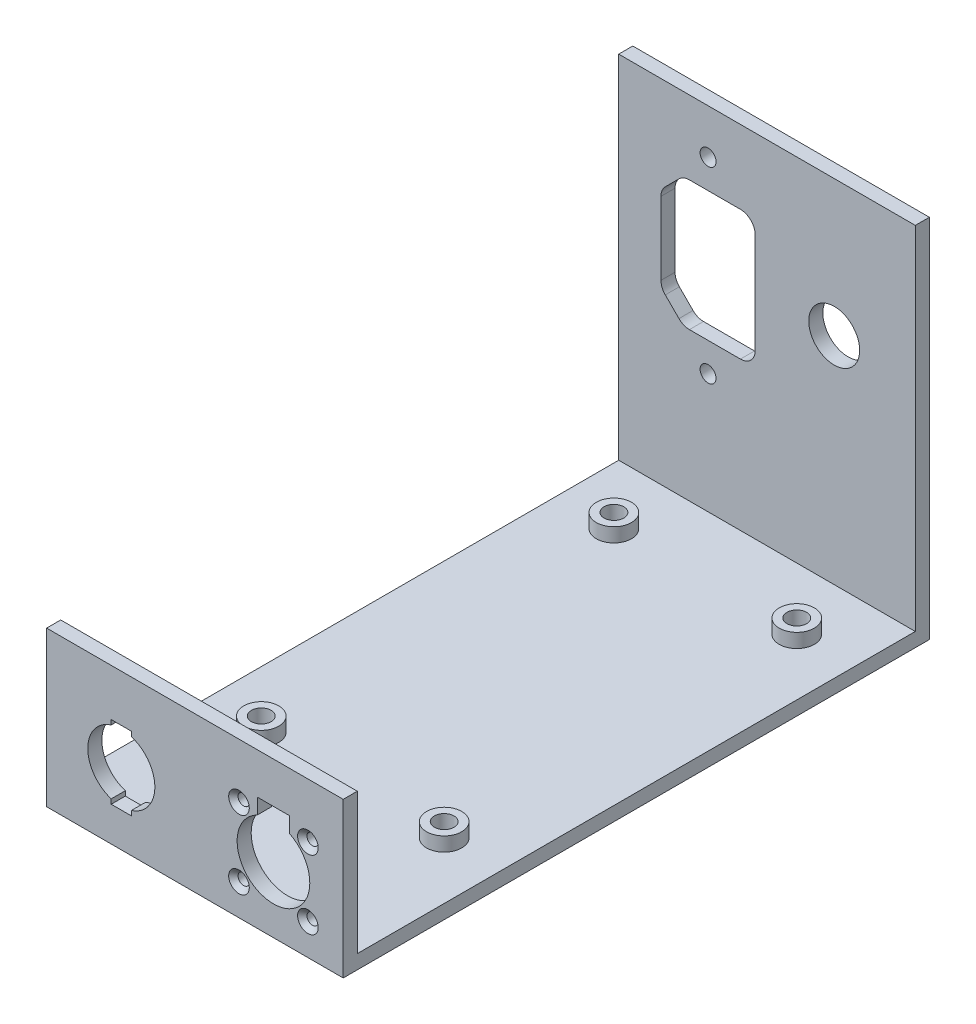
SolidWorks part; units mm, degrees
ref_plane "Спереди" through (0, 0, 0) normal (0, 0, 1) x (1, 0, 0)
ref_plane "Сверху" through (0, 0, 0) normal (0, 1, 0) x (1, 0, 0)
ref_plane "Справа" through (0, 0, 0) normal (1, 0, 0) x (0, 0, -1)
sketch "Эскиз2" plane through (0, 0, 0) normal (0, -1, 0) x (1, 0, 0)
  circle A0 centre (19.5, 37.6) radius 3.75
  circle A1 centre (19.5, -37.6) radius 3.75
  circle A2 centre (-19.5, -37.6) radius 3.75
  circle A3 centre (-19.5, 37.6) radius 3.75
  dimension "D1" = 7.5
extrude "Бобышка-Вытянуть1" add sketch "Эскиз2" along normal blind 3
sketch "Эскиз3" plane through (0, -3, 0) normal (0, -1, 0) x (1, 0, 0)
  line L0 (26.625, 41.25) -> (26.625, -41.25) construction
  line L1 (-31.625, 71.25) -> (31.625, 71.25)
  line L2 (-31.625, 71.25) -> (-31.625, -53.75)
  line L3 (-31.625, -53.75) -> (31.625, -53.75)
  line L4 (31.625, 71.25) -> (31.625, -53.75)
  line L5 (-31.625, 71.25) -> (31.625, -53.75) construction
  line L6 (-31.625, -53.75) -> (31.625, 71.25) construction
  line L8 (-23.625, 41.25) -> (23.625, 41.25) construction
  line L9 (-26.625, 41.25) -> (-26.625, -41.25) construction
  point P0 (0, 8.75)
  dimension "D1" = 5
  dimension "D2" = 125
  dimension "D3" = 30
  dimension "D4" = 5
extrude "Бобышка-Вытянуть2" add sketch "Эскиз3" along normal blind 3
sketch "Эскиз4" plane through (0, 0, 0) normal (0, 1, 0) x (1, 0, 0)
  circle A0 centre (19.5, 37.6) radius 2.1
  circle A1 centre (19.5, -37.6) radius 2.1
  circle A2 centre (-19.5, -37.6) radius 2.1
  circle A3 centre (-19.5, 37.6) radius 2.1
  dimension "D1" = 4.2
extrude "Вырез-Вытянуть1" cut sketch "Эскиз4" against normal blind 4
sketch "Эскиз5" plane through (0, -3, 0) normal (0, 1, 0) x (1, 0, 0)
  line L0 (31.625, 53.75) -> (31.625, -71.25) construction
  line L1 (-31.625, -71.25) -> (31.625, -71.25)
  line L2 (-31.625, -71.25) -> (-31.625, -68.25)
  line L3 (-31.625, -68.25) -> (31.625, -68.25)
  line L4 (31.625, -71.25) -> (31.625, -68.25)
  dimension "D1" = 3
extrude "Бобышка-Вытянуть3" add sketch "Эскиз5" along normal blind 30
sketch "Эскиз8" plane through (0, 0, 71.25) normal (0, 0, 1) x (1, 0, 0)
  line L6 (20.1954, 14.9397) -> (20.1954, 18.25)
  line L7 (20.1954, 18.25) -> (13.2954, 18.25)
  line L8 (13.2954, 18.25) -> (13.2954, 14.9397)
  line L9 (20.1954, 14.9397) -> (20.1954, 18.25)
  line L10 (20.1954, 18.25) -> (13.2954, 18.25)
  line L11 (13.2954, 18.25) -> (13.2954, 14.9397)
  arc A2 (13.2954, 14.9397) -> (20.1954, 14.9397) centre (16.7454, 8) ccw
  arc A3 (13.2954, 14.9397) -> (20.1954, 14.9397) centre (16.7454, 8) ccw
  dimension "D1" = 0.15
extrude "Вырез-Вытянуть2" cut sketch "Эскиз8" against normal blind 10
hole_wizard "Зенковка для винта с полупотайной головкой M21" positions "Эскиз9" profile "Эскиз11" countersink size "M2" standard "DIN"
sketch "Эскиз9" plane through (0, 0, 71.25) normal (0, 0, 1) x (1, 0, 0)
  circle A0 centre (9.3954, 0.65) radius 1.2 construction
  circle A1 centre (24.0954, 0.65) radius 1.2 construction
  circle A2 centre (9.3954, 15.35) radius 1.2 construction
  circle A3 centre (24.0954, 15.35) radius 1.2 construction
  circle A4 centre (9.3954, 0.65) radius 1.2 construction
  circle A5 centre (24.0954, 0.65) radius 1.2 construction
  circle A6 centre (9.3954, 15.35) radius 1.2 construction
  circle A7 centre (24.0954, 15.35) radius 1.2 construction
  point P1 (9.3954, 0.65)
  point P3 (24.0954, 0.65)
  point P5 (9.3954, 15.35)
  point P7 (24.0954, 15.35)
sketch "Эскиз11" plane through (9.3954, 0.65, 71.25) normal (1, 0, 0) x (0, -1, 0)
  line L0 (0, 0) -> (0, 5.721)
  line L1 (0, 5.721) -> (1.2, 5)
  line L2 (1.2, 5) -> (1.2, 1)
  line L3 (1.2, 1) -> (2.2, 0)
  line L5 (2.2, 0) -> (0, 0)
  line L6 (-1.2, 1) -> (-2.2, 0) construction
  line L10 (0, 5.721) -> (-1.2, 5) construction
  line L11 (0, -6.35) -> (0, 107.95) construction
  dimension "Диаметр отверстия" = 2.4
  dimension "Глубина отверстия" = 5
  dimension "Диаметр передней зенковки" = 4.4
  dimension "Угол передней зенковки" = 90
  dimension "Угол заточки сверла" = 118
sketch "Эскиз12" plane through (0, -3, 0) normal (0, 1, 0) x (1, 0, 0)
  line L0 (-31.625, -68.25) -> (-31.625, 53.75) construction
  line L1 (31.625, 53.75) -> (-31.625, 53.75)
  line L2 (31.625, 53.75) -> (31.625, 50.75)
  line L3 (31.625, 50.75) -> (-31.625, 50.75)
  line L4 (-31.625, 53.75) -> (-31.625, 50.75)
  dimension "D1" = 3
extrude "Бобышка-Вытянуть4" add sketch "Эскиз12" along normal blind 75
sketch "Эскиз13" plane through (0, 0, -50.75) normal (0, 0, 1) x (1, 0, 0)
  line L12 (-16.5476, 28.6612) -> (-5.6652, 28.6612)
  line L13 (-2.5152, 31.8112) -> (-2.5152, 53.1612)
  line L14 (-5.6652, 56.3112) -> (-16.5476, 56.3112)
  line L15 (-18.775, 55.3886) -> (-21.6926, 52.471)
  line L16 (-22.6152, 50.2436) -> (-22.6152, 34.7289)
  line L17 (-21.6926, 32.5015) -> (-18.775, 29.5839)
  line L18 (-16.5476, 28.6612) -> (-5.6652, 28.6612)
  line L19 (-2.5152, 31.8112) -> (-2.5152, 53.1612)
  line L20 (-5.6652, 56.3112) -> (-16.5476, 56.3112)
  line L21 (-18.775, 55.3886) -> (-21.6926, 52.471)
  line L22 (-22.6152, 50.2436) -> (-22.6152, 34.7289)
  line L23 (-21.6926, 32.5015) -> (-18.775, 29.5839)
  arc A12 (-18.775, 29.5839) -> (-16.5476, 28.6612) centre (-16.5476, 31.8112) ccw
  arc A13 (-5.6652, 28.6612) -> (-2.5152, 31.8112) centre (-5.6652, 31.8112) ccw
  arc A14 (-2.5152, 53.1612) -> (-5.6652, 56.3112) centre (-5.6652, 53.1612) ccw
  arc A15 (-16.5476, 56.3112) -> (-18.775, 55.3886) centre (-16.5476, 53.1612) ccw
  arc A16 (-21.6926, 52.471) -> (-22.6152, 50.2436) centre (-19.4652, 50.2436) ccw
  arc A17 (-22.6152, 34.7289) -> (-21.6926, 32.5015) centre (-19.4652, 34.7289) ccw
  arc A18 (-18.775, 29.5839) -> (-16.5476, 28.6612) centre (-16.5476, 31.8112) ccw
  arc A19 (-5.6652, 28.6612) -> (-2.5152, 31.8112) centre (-5.6652, 31.8112) ccw
  arc A20 (-2.5152, 53.1612) -> (-5.6652, 56.3112) centre (-5.6652, 53.1612) ccw
  arc A21 (-16.5476, 56.3112) -> (-18.775, 55.3886) centre (-16.5476, 53.1612) ccw
  arc A22 (-21.6926, 52.471) -> (-22.6152, 50.2436) centre (-19.4652, 50.2436) ccw
  arc A23 (-22.6152, 34.7289) -> (-21.6926, 32.5015) centre (-19.4652, 34.7289) ccw
  dimension "D1" = 0.15
extrude "Вырез-Вытянуть3" cut sketch "Эскиз13" against normal through all
hole_wizard "Отверстие с зазором M31" positions "Эскиз14" profile "Эскиз15" hole size "M3" standard "DIN"
sketch "Эскиз14" plane through (0, 0, -53.75) normal (0, 0, -1) x (-1, 0, 0)
  point P0 (12.5652, 22.4862)
  point P3 (12.5652, 62.4862)
sketch "Эскиз15" plane through (-12.5652, 22.4862, -53.75) normal (1, 0, 0) x (0, 1, 0)
  line L0 (0, 0) -> (0, 11.0215)
  line L1 (0, 11.0215) -> (1.7, 10)
  line L2 (1.7, 10) -> (1.7, 0)
  line L5 (1.7, 0) -> (0, 0)
  line L10 (0, 11.0215) -> (-1.7, 10) construction
  line L11 (0, -6.35) -> (0, 107.95) construction
  dimension "Диаметр отверстия" = 3.4
  dimension "Глубина отверстия" = 10
  dimension "Угол заточки сверла" = 118
sketch "Эскиз16" plane through (0, 0, -50.75) normal (0, 0, 1) x (1, 0, 0)
  circle A2 centre (14.3322, 42.9731) radius 5.425
  circle A3 centre (14.3322, 42.9731) radius 5.425
  dimension "D1" = 0.15
extrude "Вырез-Вытянуть4" cut sketch "Эскиз16" against normal through all
sketch "Эскиз17" plane through (0, 0, 68.25) normal (0, 0, -1) x (-1, 0, 0)
  line L2 (17.6969, 0.8798) -> (13.6969, 0.8798) construction
  line L3 (17.6969, 17.4672) -> (13.6969, 17.4672) construction
  line L8 (17.6969, 1.0406) -> (17.6969, 0.8798) construction
  line L9 (13.6969, 1.0406) -> (13.6969, 0.8798) construction
  line L10 (13.6969, 17.3064) -> (13.6969, 17.4672) construction
  line L11 (17.6969, 17.3064) -> (17.6969, 17.4672) construction
  line L12 (17.6969, 0.8798) -> (13.6969, 0.8798) construction
  line L13 (17.6969, 17.4672) -> (13.6969, 17.4672) construction
  line L14 (17.6969, 2.4653) -> (17.6969, 0.8798) construction
  line L15 (13.6969, 2.4653) -> (13.6969, 0.8798) construction
  line L16 (13.6969, 15.8817) -> (13.6969, 17.4672) construction
  line L17 (17.6969, 15.8817) -> (17.6969, 17.4672) construction
  line L18 (13.5469, 15.9926) -> (13.5469, 16.9926)
  line L19 (13.5469, 2.3544) -> (13.5469, 1.3544)
  line L22 (17.8469, 2.3544) -> (17.8469, 1.3544)
  line L23 (17.8469, 15.9926) -> (17.8469, 16.9926)
  line L24 (17.8469, 15.9926) -> (17.8469, 17.4672) construction
  line L25 (13.5469, 15.9926) -> (13.5469, 17.4672) construction
  line L26 (17.8469, 16.9926) -> (13.5469, 16.9926)
  line L27 (13.5469, 2.3544) -> (13.5469, 0.8798) construction
  line L28 (17.8469, 2.3544) -> (17.8469, 0.8798) construction
  line L29 (17.8469, 1.3544) -> (13.5469, 1.3544)
  arc A0 (18.8493, 2.9235) -> (18.8493, 15.4235) centre (15.6969, 9.1735) ccw construction
  arc A1 (13.6969, 15.8817) -> (13.6969, 2.4653) centre (15.6969, 9.1735) ccw construction
  arc A2 (17.6969, 2.4653) -> (17.6969, 15.8817) centre (15.6969, 9.1735) ccw construction
  arc A5 (13.5469, 15.9926) -> (13.5469, 2.3544) centre (15.6969, 9.1735) ccw
  arc A6 (17.8469, 2.3544) -> (17.8469, 15.9926) centre (15.6969, 9.1735) ccw
  dimension "D2" = 1
  dimension "D3" = 1
  dimension "D1" = 0.15
extrude "Вырез-Вытянуть5" cut sketch "Эскиз17" against normal through all
